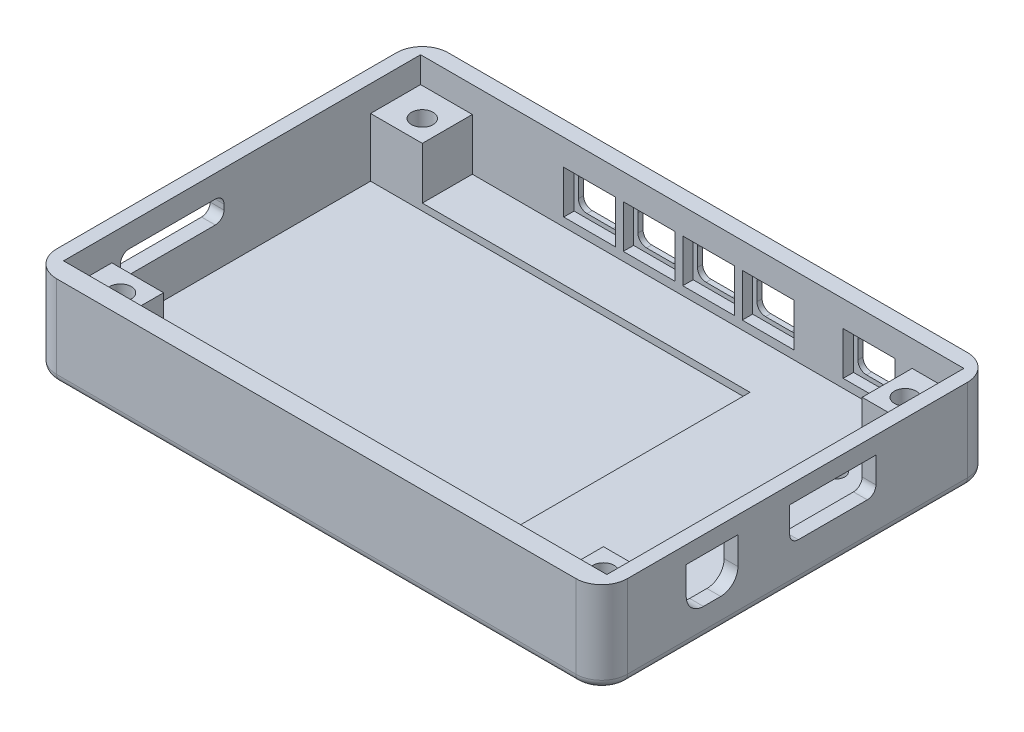
SolidWorks part; units mm, degrees
ref_plane "前视基准面" through (0, 0, 0) normal (0, 0, 1) x (1, 0, 0)
ref_plane "上视基准面" through (0, 0, 0) normal (0, 1, 0) x (1, 0, 0)
ref_plane "右视基准面" through (0, 0, 0) normal (1, 0, 0) x (0, 0, -1)
sketch "草图1" plane through (0, 0, 0) normal (0, 1, 0) x (1, 0, 0)
  line L1 (-31.5, -21) -> (31.5, -21)
  line L2 (-31.5, -21) -> (-31.5, 21)
  line L3 (-31.5, 21) -> (31.5, 21)
  line L4 (31.5, -21) -> (31.5, 21)
  line L5 (-31.5, -21) -> (31.5, 21) construction
  line L6 (-31.5, 21) -> (31.5, -21) construction
  point P0 (0, 0)
  dimension "D1" = 63
  dimension "D2" = 42
extrude "底" add sketch "草图1" against normal blind 1.6
sketch "草图2" plane through (0, 0, 0) normal (0, 1, 0) x (1, 0, 0)
  line L0 (-31.5, 21) -> (-31.5, -21) construction
  line L1 (-31.5, -15) -> (12.5, -15)
  line L2 (-31.5, -15) -> (-31.5, 15)
  line L3 (-31.5, 15) -> (12.5, 15)
  line L4 (12.5, -15) -> (12.5, 15)
  line L5 (-31.5, -15) -> (12.5, 15) construction
  line L6 (-31.5, 15) -> (12.5, -15) construction
  line L7 (31.5, 21) -> (-31.5, 21) construction
  line L8 (-31.5, -21) -> (31.5, -21) construction
  point P0 (-19.9597, 0.5003)
  dimension "D1" = 44
  dimension "D2" = 6
  dimension "D3" = 0
  dimension "D4" = 6
extrude "电池槽" cut sketch "草图2" against normal blind 0.8
sketch "草图4" plane through (0, -1.6, 0) normal (0, -1, 0) x (-1, 0, 0)
  line L0 (-31.5, 21) -> (-31.5, -21)
  line L1 (-31.5, 21) -> (-33.1, 21)
  line L2 (-31.5, -21) -> (-33.1, -21)
  line L3 (-33.1, 21) -> (-33.1, -21)
  line L4 (31.5, 21) -> (31.5, -21)
  line L5 (31.5, 21) -> (33.1, 21)
  line L6 (31.5, -21) -> (33.1, -21)
  line L7 (33.1, 21) -> (33.1, -21)
  dimension "D1" = 1.6
  dimension "D2" = 1.6
extrude "侧边" add sketch "草图4" against normal blind 10.6
sketch "草图5" plane through (0, 0, 0) normal (0, 1, 0) x (1, 0, 0)
  line L0 (-31.5, 21) -> (-31.5, 15)
  line L1 (-31.5, 21) -> (-25.5, 21)
  line L2 (-31.5, 15) -> (-25.5, 15)
  line L3 (-25.5, 21) -> (-25.5, 15)
  line L4 (-31.5, 21) -> (-31.5, 15) construction
  line L5 (25.5, 21) -> (25.5, 15)
  line L6 (25.5, 21) -> (31.5, 21)
  line L7 (25.5, 15) -> (31.5, 15)
  line L8 (31.5, 21) -> (31.5, 15)
  line L9 (-31.5, -15) -> (-31.5, -21)
  line L10 (-31.5, -15) -> (-25.5, -15)
  line L11 (-31.5, -21) -> (-25.5, -21)
  line L12 (-25.5, -15) -> (-25.5, -21)
  line L13 (25.5, -15) -> (25.5, -21)
  line L14 (25.5, -15) -> (31.5, -15)
  line L15 (25.5, -21) -> (31.5, -21)
  line L16 (31.5, -15) -> (31.5, -21)
  dimension "D1" = 6
  dimension "D2" = 6
  dimension "D3" = 6
  dimension "D4" = 6
extrude "螺丝固定" add sketch "草图5" along normal offset from surface (6 mm away) 3 up to face at (-32.3, 9, 0)
sketch "草图6" plane through (0, 9, 0) normal (0, 1, 0) x (1, 0, 0)
  line L0 (-25.5, 15) -> (-25.5, 21) construction
  line L1 (-31.5, 15) -> (-25.5, 15) construction
  circle A0 centre (-28, 17.5) radius 1.25
  circle A1 centre (28, 17.5) radius 1.25
  circle A2 centre (28, -17.5) radius 1.25
  circle A3 centre (-28, -17.5) radius 1.25
  dimension "D1" = 2.5
  dimension "D2" = 2.5
  dimension "D3" = 2.5
  dimension "D4" = 2
  dimension "D5" = 2
extrude "螺丝孔" cut sketch "草图6" against normal up to surface (9 mm away) up to face at (7.3333, 0, 0)
sketch "草图8" plane through (0, 0, 0) normal (0, 1, 0) x (1, 0, 0)
  line L0 (25.5, 21) -> (25.5, 15) construction
  line L1 (-30.5, 20) -> (-25.5, 20)
  line L2 (-30.5, 20) -> (-30.5, 15)
  line L3 (-30.5, 15) -> (-25.5, 15)
  line L4 (-25.5, 20) -> (-25.5, 15)
  line L5 (-30.5, 20) -> (-25.5, 15) construction
  line L6 (-30.5, 15) -> (-25.5, 20) construction
  line L7 (30.5, 20) -> (25.5, 20)
  line L8 (30.5, 20) -> (30.5, 15)
  line L9 (30.5, 15) -> (25.5, 15)
  line L10 (25.5, 20) -> (25.5, 15)
  line L11 (30.5, 20) -> (25.5, 15) construction
  line L12 (30.5, 15) -> (25.5, 20) construction
  line L14 (-30.5, -20) -> (-25.5, -20)
  line L15 (-30.5, -20) -> (-30.5, -15)
  line L16 (-30.5, -15) -> (-25.5, -15)
  line L17 (-25.5, -20) -> (-25.5, -15)
  line L18 (-30.5, -20) -> (-25.5, -15) construction
  line L19 (-30.5, -15) -> (-25.5, -20) construction
  line L20 (30.5, -20) -> (25.5, -20)
  line L21 (30.5, -20) -> (30.5, -15)
  line L22 (30.5, -15) -> (25.5, -15)
  line L23 (25.5, -20) -> (25.5, -15)
  line L24 (30.5, -20) -> (25.5, -15) construction
  line L25 (30.5, -15) -> (25.5, -20) construction
  circle A0 centre (28, 17.5) radius 1.25 construction
  circle A1 centre (28, -17.5) radius 1.25 construction
  circle A2 centre (-28, -17.5) radius 1.25 construction
  circle A3 centre (-28, 17.5) radius 1.25 construction
  circle A4 centre (28, 17.5) radius 1.25 construction
  circle A5 centre (28, -17.5) radius 1.25 construction
  circle A6 centre (-28, -17.5) radius 1.25 construction
  circle A7 centre (-28, 17.5) radius 1.25 construction
sketch "草图9" plane through (0, 0, -21) normal (0, 0, -1) x (-1, 0, 0)
  line L0 (-33.1, 9) -> (-33.1, -1.6)
  line L1 (-33.1, 9) -> (33.1, 9)
  line L2 (-33.1, -1.6) -> (33.1, -1.6)
  line L3 (33.1, 9) -> (33.1, -1.6)
extrude "凸台-拉伸4" add sketch "草图9" along normal blind 1.6
sketch "草图10" plane through (0, 0, -21) normal (0, 0, 1) x (1, 0, 0)
  line L1 (17.5, 1) -> (23.5, 1)
  line L2 (17.5, 1) -> (17.5, 6)
  line L3 (17.5, 6) -> (23.5, 6)
  line L4 (23.5, 1) -> (23.5, 6)
  line L5 (17.5, 1) -> (23.5, 6) construction
  line L6 (17.5, 6) -> (23.5, 1) construction
  line L7 (25.5, 0) -> (-25.5, 0) construction
  line L8 (25.5, 6) -> (25.5, 0) construction
  line L9 (5.8, 1) -> (11.8, 1)
  line L10 (5.8, 1) -> (5.8, 6)
  line L11 (5.8, 6) -> (11.8, 6)
  line L12 (11.8, 1) -> (11.8, 6)
  line L13 (5.8, 1) -> (11.8, 6) construction
  line L14 (5.8, 6) -> (11.8, 1) construction
  line L15 (-1.1, 1) -> (4.9, 1)
  line L16 (-1.1, 1) -> (-1.1, 6)
  line L17 (-1.1, 6) -> (4.9, 6)
  line L18 (4.9, 1) -> (4.9, 6)
  line L19 (-1.1, 1) -> (4.9, 6) construction
  line L20 (-1.1, 6) -> (4.9, 1) construction
  line L21 (-8, 1) -> (-2, 1)
  line L22 (-8, 1) -> (-8, 6)
  line L23 (-8, 6) -> (-2, 6)
  line L24 (-2, 1) -> (-2, 6)
  line L25 (-8, 1) -> (-2, 6) construction
  line L26 (-8, 6) -> (-2, 1) construction
  line L27 (-14.9, 1) -> (-8.9, 1)
  line L28 (-14.9, 1) -> (-14.9, 6)
  line L29 (-14.9, 6) -> (-8.9, 6)
  line L30 (-8.9, 1) -> (-8.9, 6)
  line L31 (-14.9, 1) -> (-8.9, 6) construction
  line L32 (-14.9, 6) -> (-8.9, 1) construction
  point P0 (20.5, 3.5)
  point P11 (8.8, 3.5)
  point P16 (1.9, 3.5)
  point P21 (-5, 3.5)
  point P26 (-11.9, 3.5)
  dimension "D1" = 6
  dimension "D2" = 5
  dimension "D3" = 5
  dimension "D4" = 3.5
  dimension "D5" = 2
  dimension "D6" = 4
extrude "按键底" cut sketch "草图10" against normal blind 1
sketch "草图12" plane through (0, 0, -22) normal (0, 0, 1) x (1, 0, 0)
  line L0 (17.5, 6) -> (23.5, 1) construction
  line L1 (6.3, 2.5) -> (6.3, 4.5)
  line L2 (19, 1.5) -> (22, 1.5)
  line L3 (18, 2.5) -> (18, 4.5)
  line L4 (23.5, 1) -> (23.5, 6)
  line L5 (23.5, 6) -> (17.5, 6)
  line L6 (17.5, 6) -> (17.5, 1)
  line L7 (17.5, 1) -> (23.5, 1)
  line L8 (23.5, 1) -> (23.5, 6) construction
  line L9 (23.5, 6) -> (17.5, 6) construction
  line L10 (17.5, 6) -> (17.5, 1) construction
  line L11 (17.5, 1) -> (23.5, 1) construction
  line L12 (19, 5.5) -> (22, 5.5)
  line L13 (23, 2.5) -> (23, 4.5)
  line L14 (18, 1.5) -> (23, 5.5) construction
  line L15 (18, 5.5) -> (23, 1.5) construction
  line L16 (7.3, 1.5) -> (10.3, 1.5)
  line L17 (7.3, 5.5) -> (10.3, 5.5)
  line L18 (11.3, 2.5) -> (11.3, 4.5)
  line L19 (-0.6, 2.5) -> (-0.6, 4.5)
  line L20 (0.4, 1.5) -> (3.4, 1.5)
  line L21 (0.4, 5.5) -> (3.4, 5.5)
  line L22 (4.4, 2.5) -> (4.4, 4.5)
  line L23 (-7.5, 2.5) -> (-7.5, 4.5)
  line L24 (-6.5, 1.5) -> (-3.5, 1.5)
  line L25 (-6.5, 5.5) -> (-3.5, 5.5)
  line L26 (-2.5, 2.5) -> (-2.5, 4.5)
  line L27 (-14.4, 2.5) -> (-14.4, 4.5)
  line L28 (-13.4, 1.5) -> (-10.4, 1.5)
  line L29 (-13.4, 5.5) -> (-10.4, 5.5)
  line L30 (-9.4, 2.5) -> (-9.4, 4.5)
  arc A0 (22, 5.5) -> (23, 4.5) centre (22, 4.5) cw
  arc A1 (22, 1.5) -> (23, 2.5) centre (22, 2.5) ccw
  arc A2 (19, 1.5) -> (18, 2.5) centre (19, 2.5) cw
  arc A3 (18, 4.5) -> (19, 5.5) centre (19, 4.5) cw
  arc A4 (6.3, 4.5) -> (7.3, 5.5) centre (7.3, 4.5) cw
  arc A5 (7.3, 1.5) -> (6.3, 2.5) centre (7.3, 2.5) cw
  arc A6 (10.3, 5.5) -> (11.3, 4.5) centre (10.3, 4.5) cw
  arc A7 (10.3, 1.5) -> (11.3, 2.5) centre (10.3, 2.5) ccw
  arc A8 (-0.6, 4.5) -> (0.4, 5.5) centre (0.4, 4.5) cw
  arc A9 (0.4, 1.5) -> (-0.6, 2.5) centre (0.4, 2.5) cw
  arc A10 (3.4, 5.5) -> (4.4, 4.5) centre (3.4, 4.5) cw
  arc A11 (3.4, 1.5) -> (4.4, 2.5) centre (3.4, 2.5) ccw
  arc A12 (-7.5, 4.5) -> (-6.5, 5.5) centre (-6.5, 4.5) cw
  arc A13 (-6.5, 1.5) -> (-7.5, 2.5) centre (-6.5, 2.5) cw
  arc A14 (-3.5, 5.5) -> (-2.5, 4.5) centre (-3.5, 4.5) cw
  arc A15 (-3.5, 1.5) -> (-2.5, 2.5) centre (-3.5, 2.5) ccw
  arc A16 (-14.4, 4.5) -> (-13.4, 5.5) centre (-13.4, 4.5) cw
  arc A17 (-13.4, 1.5) -> (-14.4, 2.5) centre (-13.4, 2.5) cw
  arc A18 (-10.4, 5.5) -> (-9.4, 4.5) centre (-10.4, 4.5) cw
  arc A19 (-10.4, 1.5) -> (-9.4, 2.5) centre (-10.4, 2.5) ccw
  point P2 (20.5, 3.5)
  dimension "D4" = 1
  dimension "D2" = 5
  dimension "D3" = 4
  dimension "D1" = 0
  dimension "D5" = 2
  dimension "D6" = 4
extrude "按键头" cut sketch "草图12" against normal up to next
fillet "圆角4" radius 1 3 edges at (-33.1, -1.6, -0.8) (33.1, -1.6, -0.8) (0, -1.6, -22.6)
fillet "圆角5" radius 3 4 edges at (-32.8071, -1.3071, -22.3071) (32.8071, -1.3071, -22.3071) (33.1, 4.2, -22.6) (-33.1, 4.2, -22.6)
sketch "草图15" plane through (0, 9, 0) normal (0, 1, 0) x (1, 0, 0)
  line L8 (-31.5, 21) -> (31.5, 21)
  line L10 (-31.5, 21) -> (31.5, 21)
  line L16 (33.1, -21) -> (33.1, 19.6)
  line L17 (30.1, 22.6) -> (-30.1, 22.6)
  line L18 (-33.1, 19.6) -> (-33.1, -21)
  line L19 (-33.1, -21) -> (-31.5, -21)
  line L22 (-31.5, -21) -> (-31.5, 21)
  line L28 (31.5, 21) -> (31.5, -21)
  line L31 (31.5, -21) -> (33.1, -21)
  line L32 (33.1, -21) -> (33.1, 19.6)
  line L33 (30.1, 22.6) -> (-30.1, 22.6)
  line L34 (-33.1, 19.6) -> (-33.1, -21)
  line L35 (-33.1, -21) -> (-31.5, -21)
  line L38 (-31.5, -21) -> (-31.5, 21)
  line L44 (31.5, 21) -> (31.5, -21)
  line L47 (31.5, -21) -> (33.1, -21)
  arc A2 (33.1, 19.6) -> (30.1, 22.6) centre (30.1, 19.6) ccw
  arc A3 (-30.1, 22.6) -> (-33.1, 19.6) centre (-30.1, 19.6) ccw
  arc A4 (33.1, 19.6) -> (30.1, 22.6) centre (30.1, 19.6) ccw
  arc A5 (-30.1, 22.6) -> (-33.1, 19.6) centre (-30.1, 19.6) ccw
  dimension "D1" = 0
sketch "草图16" plane through (-31.5, 0, 0) normal (1, 0, 0) x (0, 0, -1)
  line L1 (-14, 5.4) -> (-14, 4.8)
  line L2 (-2, 5.4) -> (-2, 4.8)
  line L3 (-13, 3.8) -> (-3, 3.8)
  line L4 (-21, 9) -> (21, 9) construction
  line L5 (-15, 6) -> (-15, -0.8) construction
  line L6 (-13, 6.4) -> (-3, 6.4)
  arc A0 (-14, 4.8) -> (-13, 3.8) centre (-13, 4.8) ccw
  arc A1 (-2, 4.8) -> (-3, 3.8) centre (-3, 4.8) cw
  arc A2 (-13, 6.4) -> (-14, 5.4) centre (-13, 5.4) ccw
  arc A3 (-3, 6.4) -> (-2, 5.4) centre (-3, 5.4) cw
  point P10 (-14, 3.8)
  point P13 (-2, 3.8)
  dimension "D4" = 1
  dimension "D2" = 1
  dimension "D1" = 12
  dimension "D3" = 1
  dimension "D5" = 2.6
extrude "tf口" cut sketch "草图16" against normal up to next
sketch "草图17" plane through (31.5, 0, 0) normal (-1, 0, 0) x (0, 0, 1)
  line L1 (7, 7) -> (7, 3.8)
  line L2 (13, 7) -> (13, 3.8)
  line L3 (9, 1.8) -> (11, 1.8)
  line L4 (-21, 9) -> (21, 9) construction
  line L5 (15, -0.8) -> (15, 6) construction
  line L7 (1, 7) -> (1, 4)
  line L8 (-9, 7) -> (-9, 4)
  line L9 (0, 3) -> (-8, 3)
  line L10 (-9, 7) -> (1, 7)
  line L12 (7, 7) -> (13, 7)
  arc A0 (13, 3.8) -> (11, 1.8) centre (11, 3.8) cw
  arc A1 (7, 3.8) -> (9, 1.8) centre (9, 3.8) ccw
  arc A2 (1, 4) -> (0, 3) centre (0, 4) cw
  arc A3 (-9, 4) -> (-8, 3) centre (-8, 4) ccw
  point P10 (13, 1.8)
  point P13 (7, 1.8)
  point P22 (1, 3)
  point P25 (-9, 3)
  dimension "D4" = 2
  dimension "D8" = 1
  dimension "D1" = 6
  dimension "D3" = 2
  dimension "D5" = 10
  dimension "D6" = 14
  dimension "D9" = 2
extrude "耳机和usb口" cut sketch "草图17" against normal up to next
sketch "草图18" plane through (0, 0, 21) normal (0, 0, 1) x (1, 0, 0)
  line L0 (33.1, 9) -> (33.1, -0.6) construction
  line L1 (-32.1, -1.6) -> (32.1, -1.6) construction
  line L2 (-33.1, 9) -> (-33.1, -0.6) construction
  line L3 (33.1, 9) -> (33.1, -0.6)
  line L4 (-32.1, -1.6) -> (32.1, -1.6)
  line L5 (-33.1, 9) -> (-33.1, -0.6)
  line L6 (-33.1, 9) -> (33.1, 9)
  arc A0 (32.1, -1.6) -> (33.1, -0.6) centre (32.1, -0.6) ccw construction
  arc A1 (-33.1, -0.6) -> (-32.1, -1.6) centre (-32.1, -0.6) ccw construction
  arc A2 (32.1, -1.6) -> (33.1, -0.6) centre (32.1, -0.6) ccw
  arc A3 (-33.1, -0.6) -> (-32.1, -1.6) centre (-32.1, -0.6) ccw
extrude "封底" add sketch "草图18" along normal blind 1.8
fillet "圆角7" radius 3 2 edges at (33.1, 4.2, 22.8) (-33.1, 4.2, 22.8) tangent propagation no
fillet "圆角8" radius 1 3 edges at (-31.1705, -1.6, 22.6025) (31.1705, -1.6, 22.6025) (0, -1.6, 22.8)
sketch "草图19" plane through (0, 0, 21) normal (0, 0, -1) x (-1, 0, 0)
  line L8 (31.5, 9) -> (-31.5, 9)
  line L9 (-31.5, 9) -> (-31.5, 6)
  line L10 (-31.5, 6) -> (-25.5, 6)
  line L11 (-25.5, 6) -> (-25.5, 0)
  line L12 (-25.5, 0) -> (25.5, 0)
  line L13 (25.5, 0) -> (25.5, 6)
  line L14 (25.5, 6) -> (31.5, 6)
  line L15 (31.5, 6) -> (31.5, 9)
  line L16 (31.5, 9) -> (-31.5, 9)
  line L17 (-31.5, 9) -> (-31.5, 6)
  line L18 (-31.5, 6) -> (-25.5, 6)
  line L19 (-25.5, 6) -> (-25.5, 0)
  line L20 (-25.5, 0) -> (25.5, 0)
  line L21 (25.5, 0) -> (25.5, 6)
  line L22 (25.5, 6) -> (31.5, 6)
  line L23 (31.5, 6) -> (31.5, 9)
  dimension "D1" = 0
extrude "凸台-拉伸5" add sketch "草图19" along normal blind 0.4
sketch "草图24" plane through (0, 0, 0) normal (0, 1, 0) x (1, 0, 0)
  line L12 (-25.5, -15) -> (-25.5, -20.6)
  line L13 (-25.5, -20.6) -> (25.5, -20.6)
  line L14 (25.5, -20.6) -> (25.5, -15)
  line L15 (25.5, -15) -> (31.5, -15)
  line L16 (31.5, -15) -> (31.5, 15)
  line L17 (31.5, 15) -> (25.5, 15)
  line L18 (25.5, 15) -> (25.5, 21)
  line L19 (25.5, 21) -> (-25.5, 21)
  line L20 (-25.5, 21) -> (-25.5, 15)
  line L21 (-25.5, 15) -> (12.5, 15)
  line L22 (12.5, 15) -> (12.5, -15)
  line L23 (12.5, -15) -> (-25.5, -15)
  line L24 (-25.5, -15) -> (-25.5, -20.6)
  line L25 (-25.5, -20.6) -> (25.5, -20.6)
  line L26 (25.5, -20.6) -> (25.5, -15)
  line L27 (25.5, -15) -> (31.5, -15)
  line L28 (31.5, -15) -> (31.5, 15)
  line L29 (31.5, 15) -> (25.5, 15)
  line L30 (25.5, 15) -> (25.5, 21)
  line L32 (-25.5, 21) -> (-25.5, 15)
  line L33 (-25.5, 15) -> (12.5, 15)
  line L34 (12.5, 15) -> (12.5, -15)
  line L35 (12.5, -15) -> (-25.5, -15)
  line L37 (25.5, 21) -> (-25.5, 21)
  dimension "D1" = 0
sketch "草图25" plane through (0, 0, 0) normal (0, 1, 0) x (1, 0, 0)
  circle A0 centre (25.5, 12) radius 1
  point P0 (28, 17.5)
  dimension "D1" = 2
  dimension "D2" = 2.5
  dimension "D3" = 5.5
extrude "BOOT孔" cut sketch "草图25" against normal up to next
sketch "草图27" plane through (0, 0, -21) normal (0, 0, 1) x (1, 0, 0)
  line L4 (5.8, 1) -> (11.8, 1)
  line L5 (11.8, 1) -> (11.8, 6)
  line L6 (11.8, 6) -> (5.8, 6)
  line L7 (5.8, 6) -> (5.8, 1)
  line L8 (31.5, 6) -> (31.5, 9)
  line L9 (31.5, 9) -> (-31.5, 9)
  line L10 (-31.5, 9) -> (-31.5, 6)
  line L11 (-31.5, 6) -> (-25.5, 6)
  line L12 (-25.5, 6) -> (-25.5, 0)
  line L13 (-25.5, 0) -> (25.5, 0)
  line L14 (25.5, 0) -> (25.5, 6)
  line L15 (25.5, 6) -> (31.5, 6)
  line L16 (31.5, 6) -> (31.5, 9)
  line L17 (31.5, 9) -> (-31.5, 9)
  line L18 (-31.5, 9) -> (-31.5, 6)
  line L19 (-31.5, 6) -> (-25.5, 6)
  line L20 (-25.5, 6) -> (-25.5, 0)
  line L21 (-25.5, 0) -> (25.5, 0)
  line L22 (25.5, 0) -> (25.5, 6)
  line L23 (25.5, 6) -> (31.5, 6)
  line L24 (5.8, 1) -> (11.8, 1)
  line L25 (11.8, 1) -> (11.8, 6)
  line L26 (11.8, 6) -> (5.8, 6)
  line L27 (5.8, 6) -> (5.8, 1)
  line L28 (17.5, 1) -> (23.5, 1)
  line L29 (23.5, 1) -> (23.5, 6)
  line L30 (23.5, 6) -> (17.5, 6)
  line L31 (17.5, 6) -> (17.5, 1)
  line L32 (17.5, 1) -> (23.5, 1)
  line L33 (23.5, 1) -> (23.5, 6)
  line L34 (23.5, 6) -> (17.5, 6)
  line L35 (17.5, 6) -> (17.5, 1)
  line L36 (-14.9, 1) -> (-8.9, 1)
  line L37 (-8.9, 1) -> (-8.9, 6)
  line L38 (-8.9, 6) -> (-14.9, 6)
  line L39 (-14.9, 6) -> (-14.9, 1)
  line L40 (-14.9, 1) -> (-8.9, 1)
  line L41 (-8.9, 1) -> (-8.9, 6)
  line L42 (-8.9, 6) -> (-14.9, 6)
  line L43 (-14.9, 6) -> (-14.9, 1)
  line L44 (-8, 1) -> (-2, 1)
  line L45 (-2, 1) -> (-2, 6)
  line L46 (-2, 6) -> (-8, 6)
  line L47 (-8, 6) -> (-8, 1)
  line L48 (-8, 1) -> (-2, 1)
  line L49 (-2, 1) -> (-2, 6)
  line L50 (-2, 6) -> (-8, 6)
  line L51 (-8, 6) -> (-8, 1)
  line L52 (-1.1, 1) -> (4.9, 1)
  line L53 (4.9, 1) -> (4.9, 6)
  line L54 (4.9, 6) -> (-1.1, 6)
  line L55 (-1.1, 6) -> (-1.1, 1)
  line L56 (-1.1, 1) -> (4.9, 1)
  line L57 (4.9, 1) -> (4.9, 6)
  line L58 (4.9, 6) -> (-1.1, 6)
  line L59 (-1.1, 6) -> (-1.1, 1)
  dimension "D1" = 0
  dimension "D2" = 0
  dimension "D3" = 0
  dimension "D4" = 0
  dimension "D5" = 0
  dimension "D6" = 0
extrude "凸台-拉伸8" add sketch "草图27" along normal blind 0.2
